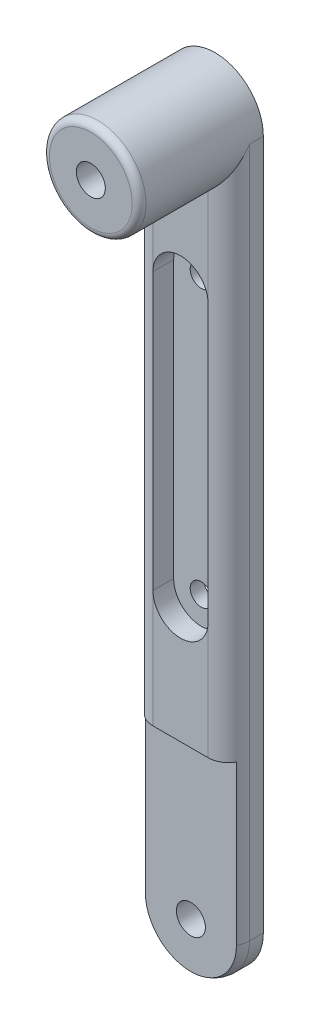
SolidWorks part; units mm, degrees
material "ABS"
ref_plane "Front Plane" through (0, 0, 0) normal (0, 0, 1) x (1, 0, 0)
ref_plane "Top Plane" through (0, 0, 0) normal (0, 1, 0) x (1, 0, 0)
ref_plane "Right Plane" through (0, 0, 0) normal (1, 0, 0) x (0, 0, -1)
sketch "Sketch1" plane through (0, 0, 0) normal (0, 0, 1) x (1, 0, 0)
  circle A0 centre (0, 0) radius 7
  dimension "D1" = 14
extrude "Boss-Extrude1" add sketch "Sketch1" along normal blind 18
sketch "Sketch2" plane through (0, 0, 0) normal (0, 0, 1) x (1, 0, 0)
  line L1 (-7, 0) -> (7, 0)
  line L2 (-7, 0) -> (-7, -100)
  line L3 (-7, -100) -> (7, -100)
  line L4 (7, 0) -> (7, -100)
  dimension "D1" = 100
  dimension "D2" = 0
  dimension "D3" = 14
  dimension "D4" = 7
extrude "Boss-Extrude2" add sketch "Sketch2" along normal blind 5
sketch "Sketch6" plane through (0, 0, 5) normal (0, 0, 1) x (1, 0, 0)
  line L0 (0, -20) -> (0, -60) construction
  line L1 (4, -20) -> (4, -60)
  line L2 (-4, -20) -> (-4, -60)
  arc A0 (4, -20) -> (-4, -20) centre (0, -20) ccw
  arc A1 (-4, -60) -> (4, -60) centre (0, -60) ccw
  point P2 (0, -40)
  dimension "D3" = 4
  dimension "D1" = 40
  dimension "D2" = 40
sketch "Sketch8" plane through (0, 0, 18) normal (0, 0, 1) x (1, 0, 0)
  circle A0 centre (0, 0) radius 2.1
  dimension "D1" = 4.2
extrude "Cut-Extrude5" cut sketch "Sketch8" against normal blind 18
sketch "Sketch9" plane through (0, 0, 5) normal (0, 0, 1) x (1, 0, 0)
  line L0 (-7, -100) -> (7, -100) construction
  circle A0 centre (0, -100) radius 7
extrude "Boss-Extrude4" add sketch "Sketch9" against normal blind 5
fillet "Fillet3" radius 3 3 edges at (0, -107, 5) (7, -50, 5) (-7, -50, 5)
extrude "Cut-Extrude6" cut sketch "Sketch6" against normal blind 3
sketch "Sketch10" plane through (0, 0, 2) normal (0, 0, 1) x (1, 0, 0)
  circle A0 centre (0, -20) radius 1.6
  circle A1 centre (0, -60) radius 1.6
  dimension "D1" = 3.2
  dimension "D2" = 3.2
extrude "Cut-Extrude7" cut sketch "Sketch10" against normal blind 3
sketch "Sketch11" plane through (0, 0, 5) normal (0, 0, 1) x (1, 0, 0)
  line L0 (-7, -100) -> (-7, 0) construction
  line L1 (-7, -77) -> (7, -77)
  line L2 (-7, -77) -> (-7, -107)
  line L3 (-7, -107) -> (7, -107)
  line L4 (7, -77) -> (7, -107)
  line L5 (-4, -100) -> (-7, -100) construction
  point P8 (-5.5, -100)
  dimension "D1" = 14
  dimension "D2" = 30
  dimension "D3" = 7
extrude "Cut-Extrude8" cut sketch "Sketch11" against normal blind 1.5
sketch "Sketch12" plane through (0, 0, 3.5) normal (0, 0, 1) x (1, 0, 0)
  circle A0 centre (0, -100) radius 2.1
  dimension "D1" = 4.2
extrude "Cut-Extrude9" cut sketch "Sketch12" against normal blind 4
fillet "Fillet4" radius 1 1 edges at (7, 0, 18)
